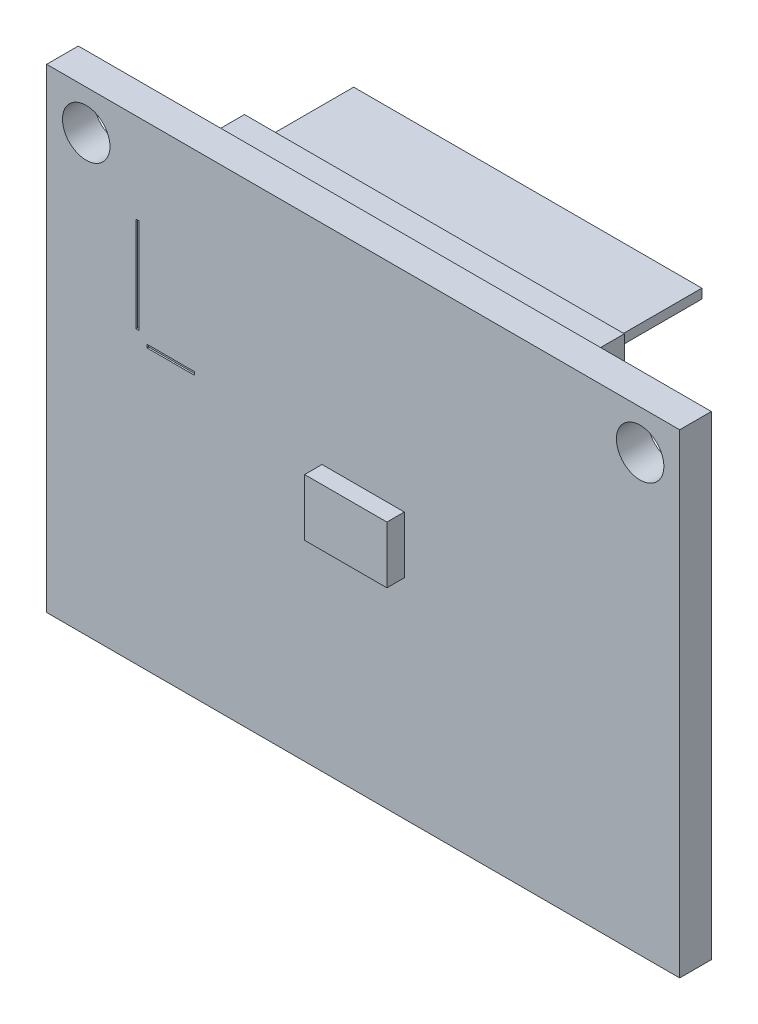
SolidWorks part; units mm, degrees
ref_plane "Top Plane" through (0, 0, 0) normal (0, 0, 1) x (1, 0, 0)
ref_plane "Right Plane" through (0, 0, 0) normal (0, 1, 0) x (1, 0, 0)
ref_plane "Front Plane" through (0, 0, 0) normal (1, 0, 0) x (0, 0, -1)
sketch "Sketch1" plane through (0, 0, 0) normal (0, 0, 1) x (1, 0, 0)
  line L0 (0, 15) -> (0, -15) construction
  line L1 (-20, 15) -> (20, 15)
  line L2 (-20, 15) -> (-20, -15)
  line L3 (-20, -15) -> (20, -15)
  line L4 (20, 15) -> (20, -15)
  line L5 (-20, 15) -> (20, -15) construction
  dimension "D1" = 40
  dimension "D2" = 30
extrude "Boss-Extrude1" add sketch "Sketch1" along normal mid plane 2
sketch "Sketch2" plane through (0, 0, -1) normal (0, 0, -1) x (-1, 0, 0)
  line L1 (20, -15) -> (-20, -15) construction
  line L2 (-12, -11.5) -> (12, -11.5)
  line L3 (-12, -11.5) -> (-12, -14)
  line L4 (-12, -14) -> (12, -14)
  line L5 (12, -11.5) -> (12, -14)
  line L6 (0, 0) -> (0, -14) construction
  line L7 (-20, 0) -> (20, 0) construction
  line L8 (-20, -15) -> (-20, 15) construction
  line L9 (20, 15) -> (20, -15) construction
  line L10 (12, 11.5) -> (12, 14)
  line L11 (-12, 14) -> (12, 14)
  line L12 (-12, 11.5) -> (-12, 14)
  line L13 (-12, 11.5) -> (12, 11.5)
  dimension "D1" = 1
  dimension "D2" = 2.5
  dimension "D3" = 24
extrude "Boss-Extrude2" add sketch "Sketch2" along normal blind 2.5
sketch "Sketch3" plane through (0, 0, -3.5) normal (0, 0, -1) x (-1, 0, 0)
  line L0 (0, 12.45) -> (0, 11.5) construction
  line L1 (-11, 13.05) -> (11, 13.05)
  line L2 (-11, 13.05) -> (-11, 12.45)
  line L3 (-11, 12.45) -> (11, 12.45)
  line L4 (11, 13.05) -> (11, 12.45)
  line L5 (-12, 11.5) -> (12, 11.5) construction
  line L6 (0, 14) -> (0, 13.05) construction
  line L7 (12, 14) -> (-12, 14) construction
  line L8 (-20, 0) -> (20, 0) construction
  line L9 (-20, -15) -> (-20, 15) construction
  line L10 (20, 15) -> (20, -15) construction
  line L11 (11, -13.05) -> (11, -12.45)
  line L12 (-11, -12.45) -> (11, -12.45)
  line L13 (-11, -13.05) -> (-11, -12.45)
  line L14 (-11, -13.05) -> (11, -13.05)
  dimension "D1" = 0.6
  dimension "D2" = 22
extrude "Boss-Extrude3" add sketch "Sketch3" along normal blind 6.1
chamfer "Chamfer1" distance 0.2 angle 45 8 edges at (11, -12.75, -9.6) (0, -12.45, -9.6) (-11, -12.75, -9.6) (0, -13.05, -9.6) (0, 13.05, -9.6) (-11, 12.75, -9.6) (0, 12.45, -9.6) (11, 12.75, -9.6)
sketch "Sketch4" plane through (0, 0, 1) normal (0, 0, 1) x (1, 0, 0)
  line L0 (-2.6, -1.8) -> (2.6, 1.8) construction
  line L1 (-2.6, -1.8) -> (2.6, -1.8)
  line L2 (-2.6, -1.8) -> (-2.6, 1.8)
  line L3 (-2.6, 1.8) -> (2.6, 1.8)
  line L4 (2.6, -1.8) -> (2.6, 1.8)
  dimension "D1" = 3.6
  dimension "D2" = 5.2
extrude "Boss-Extrude4" add sketch "Sketch4" along normal blind 1.1
sketch "Sketch5" plane through (0, 0, 1) normal (0, 0, 1) x (1, 0, 0)
  line L0 (-14.35, 3.35) -> (-13.65, 2.65) construction
  line L1 (-14.35, 9.35) -> (-14.15, 9.35)
  line L2 (-14.35, 9.35) -> (-14.35, 3.35)
  line L3 (-14.35, 3.35) -> (-14.15, 3.35)
  line L4 (-14.15, 9.35) -> (-14.15, 3.35)
  line L5 (-13.65, 2.85) -> (-10.65, 2.85)
  line L6 (-13.65, 2.85) -> (-13.65, 2.65)
  line L7 (-13.65, 2.65) -> (-10.65, 2.65)
  line L8 (-10.65, 2.85) -> (-10.65, 2.65)
  point P8 (-14, 3)
  dimension "D1" = 0.2
  dimension "D2" = 6
  dimension "D3" = 3
  dimension "D4" = 0.5
  dimension "D5" = 0.5
  dimension "D6" = 14
  dimension "D7" = 3
extrude "Cut-Extrude1" cut sketch "Sketch5" against normal blind 0.1
sketch "Sketch6" plane through (0, 0, 1) normal (0, 0, 1) x (1, 0, 0)
  line L0 (0, 15) -> (0, -15) construction
  line L1 (20, 15) -> (-20, 15) construction
  line L2 (-20, -15) -> (20, -15) construction
  line L3 (-20, 15) -> (-20, -15) construction
  circle A0 centre (-17.5, 12.5) radius 1.5
  circle A1 centre (17.5, 12.5) radius 1.5
  dimension "D1" = 2.5
  dimension "D2" = 3
  dimension "D3" = 2.5
extrude "Cut-Extrude2" cut sketch "Sketch6" against normal through all
